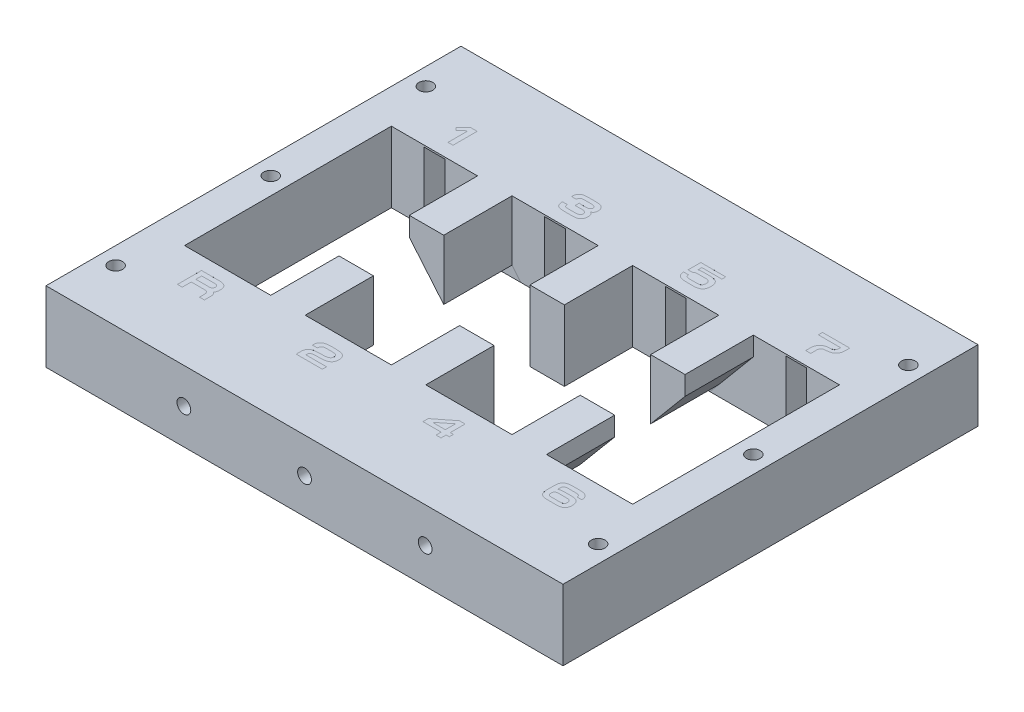
SolidWorks part; units mm, degrees
material "Oak"
ref_plane "Front Plane" through (0, 0, 0) normal (0, 0, 1) x (1, 0, 0)
ref_plane "Top Plane" through (0, 0, 0) normal (0, 1, 0) x (1, 0, 0)
ref_plane "Right Plane" through (0, 0, 0) normal (1, 0, 0) x (0, 0, -1)
sketch "Szkic3" plane through (0, 0, 0) normal (0, 1, 0) x (1, 0, 0)
  line L1 (-75, -60.2) -> (75, -60.2)
  line L2 (-75, -60.2) -> (-75, 60.2)
  line L3 (-75, 60.2) -> (75, 60.2)
  line L4 (75, -60.2) -> (75, 60.2)
  line L5 (-75, -60.2) -> (75, 60.2) construction
  line L6 (-75, 60.2) -> (75, -60.2) construction
  point P0 (0, 0)
extrude "Dodanie-wyciągnięcie1" add sketch "Szkic3" along normal blind 20.5 contours L2 L3 L4 L1
sketch "Szkic4" plane through (0, 20.5, 0) normal (0, 1, 0) x (1, 0, 0)
  line L0 (-65, 40.2) -> (-40, 40.2) construction
  line L1 (40, 40.2) -> (65, 40.2)
  line L2 (-30, 40.2) -> (-5, 40.2)
  line L3 (5, 40.2) -> (30, 40.2)
  line L4 (40, -40.2) -> (65, -40.2)
  line L5 (-65, -40.2) -> (-40, -40.2) construction
  line L6 (5, 40.2) -> (30, 40.2) construction
  line L7 (-65, 40.2) -> (-40, 40.2)
  line L8 (-65, 40.2) -> (-65, -40.2)
  line L9 (-65, -40.2) -> (-40, -40.2)
  line L10 (65, 40.2) -> (65, -40.2)
  line L12 (75, -60.2) -> (75, 60.2) construction
  line L19 (-5, 40.2) -> (-5, 10.2)
  line L20 (-5, 10.2) -> (5, 10.2)
  line L21 (5, 40.2) -> (5, 10.2)
  line L23 (30, 40.2) -> (30, 10.2)
  line L24 (30, 10.2) -> (40, 10.2)
  line L25 (40, 40.2) -> (40, 10.2)
  line L26 (-40, 40.2) -> (-40, 10.2)
  line L27 (-40, 10.2) -> (-30, 10.2)
  line L28 (-30, 40.2) -> (-30, 10.2)
  line L29 (-30, -40.2) -> (-5, -40.2)
  line L30 (5, -40.2) -> (30, -40.2)
  line L31 (-75, -60.2) -> (75, -60.2) construction
  line L32 (5, -40.2) -> (30, -40.2) construction
  line L41 (-5, -40.2) -> (-5, -10.2)
  line L42 (-5, -10.2) -> (5, -10.2)
  line L43 (5, -40.2) -> (5, -10.2)
  line L45 (30, -40.2) -> (30, -10.2)
  line L46 (30, -10.2) -> (40, -10.2)
  line L47 (40, -40.2) -> (40, -10.2)
  line L48 (-40, -40.2) -> (-40, -10.2)
  line L49 (-40, -10.2) -> (-30, -10.2)
  line L50 (-30, -40.2) -> (-30, -10.2)
  dimension "D1" = 25
  dimension "D4" = 10
  dimension "D2" = 30
  dimension "D3" = 10
  dimension "D5" = 80.4
  dimension "D6" = 20
  dimension "D7" = 30
  dimension "D8" = 30
  dimension "D9" = 30
  dimension "D10" = 30
  dimension "D11" = 30
extrude "Wytnij-wyciągnięcie1" cut sketch "Szkic4" against normal blind 20.5
sketch "Szkic5" plane through (0, 0, -40.2) normal (0, 0, 1) x (1, 0, 0)
  line L0 (-65, 0) -> (-65, 20.5) construction
  line L1 (-40, 0) -> (-65, 0)
  line L2 (-40, 0) -> (-40, 0.5)
  line L3 (-40, 0.5) -> (-65, 0.5)
  line L4 (-65, 0) -> (-65, 0.5)
extrude "Dodanie-wyciągnięcie2" add sketch "Szkic5" along normal blind 10.2
sketch "Szkic6" plane through (0, 0, -40.2) normal (0, 0, 1) x (1, 0, 0)
  line L0 (-40, 0.5) -> (-40, 20.5) construction
  line L1 (-65, 20.5) -> (-40, 20.5)
  line L2 (-65, 20.5) -> (-65, 20)
  line L3 (-65, 20) -> (-40, 20)
  line L4 (-40, 20.5) -> (-40, 20)
extrude "Dodanie-wyciągnięcie3" add sketch "Szkic6" along normal blind 10.2
sketch "Szkic7" plane through (-65, 0, 0) normal (1, 0, 0) x (0, 0, -1)
  line L1 (40.2, 0.5) -> (30, 0.5)
  line L2 (40.2, 0.5) -> (40.2, 20)
  line L3 (40.2, 20) -> (30, 20)
  line L4 (30, 0.5) -> (30, 20)
extrude "Dodanie-wyciągnięcie4" add sketch "Szkic7" along normal blind 9.5
sketch "Szkic8" plane through (-40, 0, 0) normal (-1, 0, 0) x (0, 0, 1)
  line L1 (-40.2, 0.5) -> (-30, 0.5)
  line L2 (-40.2, 0.5) -> (-40.2, 20)
  line L3 (-40.2, 20) -> (-30, 20)
  line L4 (-30, 0.5) -> (-30, 20)
extrude "Dodanie-wyciągnięcie5" add sketch "Szkic8" along normal blind 9.5
sketch "Szkic9" plane through (0, 0, -40.2) normal (0, 0, 1) x (1, 0, 0)
  line L0 (65, 0) -> (65, 20.5) construction
  line L1 (-30, 0) -> (65, 0)
  line L2 (-30, 0) -> (-30, 0.5)
  line L3 (-30, 0.5) -> (65, 0.5)
  line L4 (65, 0) -> (65, 0.5)
extrude "Dodanie-wyciągnięcie6" add sketch "Szkic9" along normal blind 10.2
sketch "Szkic10" plane through (0, 0, -40.2) normal (0, 0, 1) x (1, 0, 0)
  line L1 (-30, 20.5) -> (65, 20.5)
  line L2 (-30, 20.5) -> (-30, 20)
  line L3 (-30, 20) -> (65, 20)
  line L4 (65, 20.5) -> (65, 20)
extrude "Dodanie-wyciągnięcie7" add sketch "Szkic10" along normal blind 10.2
sketch "Szkic12" plane through (-5, 0, 0) normal (-1, 0, 0) x (0, 0, 1)
  line L1 (-40.2, 0.5) -> (-30, 0.5)
  line L2 (-40.2, 0.5) -> (-40.2, 20)
  line L3 (-40.2, 20) -> (-30, 20)
  line L4 (-30, 0.5) -> (-30, 20)
extrude "Dodanie-wyciągnięcie8" add sketch "Szkic12" along normal blind 9.5
sketch "Szkic13" plane through (-30, 0, 0) normal (1, 0, 0) x (0, 0, -1)
  line L1 (40.2, 0.5) -> (30, 0.5)
  line L2 (40.2, 0.5) -> (40.2, 20)
  line L3 (40.2, 20) -> (30, 20)
  line L4 (30, 0.5) -> (30, 20)
extrude "Dodanie-wyciągnięcie9" add sketch "Szkic13" along normal blind 9.5
sketch "Szkic14" plane through (5, 0, 0) normal (1, 0, 0) x (0, 0, -1)
  line L1 (40.2, 0.5) -> (30, 0.5)
  line L2 (40.2, 0.5) -> (40.2, 20)
  line L3 (40.2, 20) -> (30, 20)
  line L4 (30, 0.5) -> (30, 20)
extrude "Dodanie-wyciągnięcie10" add sketch "Szkic14" along normal blind 9.5
sketch "Szkic15" plane through (30, 0, 0) normal (-1, 0, 0) x (0, 0, 1)
  line L1 (-40.2, 0.5) -> (-30, 0.5)
  line L2 (-40.2, 0.5) -> (-40.2, 20)
  line L3 (-40.2, 20) -> (-30, 20)
  line L4 (-30, 0.5) -> (-30, 20)
extrude "Dodanie-wyciągnięcie11" add sketch "Szkic15" along normal blind 9.5
sketch "Szkic16" plane through (65, 0, 0) normal (-1, 0, 0) x (0, 0, 1)
  line L1 (-40.2, 0.5) -> (-30, 0.5)
  line L2 (-40.2, 0.5) -> (-40.2, 20)
  line L3 (-40.2, 20) -> (-30, 20)
  line L4 (-30, 0.5) -> (-30, 20)
extrude "Dodanie-wyciągnięcie12" add sketch "Szkic16" along normal blind 9.5
sketch "Szkic17" plane through (40, 0, 0) normal (1, 0, 0) x (0, 0, -1)
  line L1 (40.2, 0.5) -> (30, 0.5)
  line L2 (40.2, 0.5) -> (40.2, 20)
  line L3 (40.2, 20) -> (30, 20)
  line L4 (30, 0.5) -> (30, 20)
extrude "Dodanie-wyciągnięcie13" add sketch "Szkic17" along normal blind 9.5
sketch "Szkic18" plane through (0, 0, 40.2) normal (0, 0, -1) x (-1, 0, 0)
  line L0 (65, 0) -> (65, 20.5) construction
  line L1 (-65, 20.5) -> (65, 20.5)
  line L2 (-65, 20.5) -> (-65, 20)
  line L3 (-65, 20) -> (65, 20)
  line L4 (65, 20.5) -> (65, 20)
extrude "Dodanie-wyciągnięcie14" add sketch "Szkic18" along normal blind 10.2
sketch "Szkic19" plane through (0, 0, 40.2) normal (0, 0, -1) x (-1, 0, 0)
  line L1 (-65, 0) -> (65, 0)
  line L2 (-65, 0) -> (-65, 0.5)
  line L3 (-65, 0.5) -> (65, 0.5)
  line L4 (65, 0) -> (65, 0.5)
extrude "Dodanie-wyciągnięcie15" add sketch "Szkic19" along normal blind 10.2
sketch "Szkic20" plane through (65, 0, 0) normal (-1, 0, 0) x (0, 0, 1)
  line L1 (40.2, 0.5) -> (30, 0.5)
  line L2 (40.2, 0.5) -> (40.2, 20)
  line L3 (40.2, 20) -> (30, 20)
  line L4 (30, 0.5) -> (30, 20)
extrude "Dodanie-wyciągnięcie16" add sketch "Szkic20" along normal blind 9.5
sketch "Szkic21" plane through (40, 0, 0) normal (1, 0, 0) x (0, 0, -1)
  line L1 (-40.2, 0.5) -> (-30, 0.5)
  line L2 (-40.2, 0.5) -> (-40.2, 20)
  line L3 (-40.2, 20) -> (-30, 20)
  line L4 (-30, 0.5) -> (-30, 20)
extrude "Dodanie-wyciągnięcie17" add sketch "Szkic21" along normal blind 9.5
sketch "Szkic22" plane through (30, 0, 0) normal (-1, 0, 0) x (0, 0, 1)
  line L1 (40.2, 0.5) -> (30, 0.5)
  line L2 (40.2, 0.5) -> (40.2, 20)
  line L3 (40.2, 20) -> (30, 20)
  line L4 (30, 0.5) -> (30, 20)
extrude "Dodanie-wyciągnięcie18" add sketch "Szkic22" along normal blind 9.5
sketch "Szkic23" plane through (5, 0, 0) normal (1, 0, 0) x (0, 0, -1)
  line L1 (-40.2, 0.5) -> (-30, 0.5)
  line L2 (-40.2, 0.5) -> (-40.2, 20)
  line L3 (-40.2, 20) -> (-30, 20)
  line L4 (-30, 0.5) -> (-30, 20)
extrude "Dodanie-wyciągnięcie19" add sketch "Szkic23" along normal blind 9.5
sketch "Szkic24" plane through (-5, 0, 0) normal (-1, 0, 0) x (0, 0, 1)
  line L1 (40.2, 0.5) -> (30, 0.5)
  line L2 (40.2, 0.5) -> (40.2, 20)
  line L3 (40.2, 20) -> (30, 20)
  line L4 (30, 0.5) -> (30, 20)
extrude "Dodanie-wyciągnięcie20" add sketch "Szkic24" along normal blind 9.5
sketch "Szkic25" plane through (-30, 0, 0) normal (1, 0, 0) x (0, 0, -1)
  line L1 (-40.2, 0.5) -> (-30, 0.5)
  line L2 (-40.2, 0.5) -> (-40.2, 20)
  line L3 (-40.2, 20) -> (-30, 20)
  line L4 (-30, 0.5) -> (-30, 20)
extrude "Dodanie-wyciągnięcie21" add sketch "Szkic25" along normal blind 9.5
sketch "Szkic26" plane through (-40, 0, 0) normal (-1, 0, 0) x (0, 0, 1)
  line L1 (40.2, 0.5) -> (30, 0.5)
  line L2 (40.2, 0.5) -> (40.2, 20)
  line L3 (40.2, 20) -> (30, 20)
  line L4 (30, 0.5) -> (30, 20)
extrude "Dodanie-wyciągnięcie22" add sketch "Szkic26" along normal blind 9.5
sketch "Szkic27" plane through (-65, 0, 0) normal (1, 0, 0) x (0, 0, -1)
  line L1 (-40.2, 0.5) -> (-30, 0.5)
  line L2 (-40.2, 0.5) -> (-40.2, 20)
  line L3 (-40.2, 20) -> (-30, 20)
  line L4 (-30, 0.5) -> (-30, 20)
extrude "Dodanie-wyciągnięcie23" add sketch "Szkic27" along normal blind 9.5
sketch "Szkic28" plane through (0, 0, 40.2) normal (0, 0, -1) x (-1, 0, 0)
  line L0 (-52.5, 0.5) -> (-52.5, 1.5) construction
  line L1 (-49.5, 0.5) -> (-55.5, 0.5) construction
  line L2 (-52.5, 20) -> (-52.5, 19) construction
  line L3 (-55.5, 20) -> (-49.5, 20) construction
  line L4 (-52.5, 19) -> (-52.5, 1.5) construction
  line L5 (-49.5, 20) -> (-49.5, 0.5) construction
  line L6 (-55.5, 1.5) -> (-49.5, 1.5)
  line L7 (-55.5, 1.5) -> (-55.5, 19)
  line L8 (-55.5, 19) -> (-49.5, 19)
  line L9 (-49.5, 1.5) -> (-49.5, 19)
  line L10 (-55.5, 1.5) -> (-49.5, 19) construction
  line L11 (-55.5, 19) -> (-49.5, 1.5) construction
  point P8 (-52.5, 10.25)
extrude "Wytnij-wyciągnięcie2" cut sketch "Szkic28" against normal blind 10
sketch "Szkic29" plane through (0, 1.5, 0) normal (0, 1, 0) x (1, 0, 0)
  line L0 (52.5, -40.2) -> (52.5, -42.2) construction
  line L1 (55.5, -40.2) -> (49.5, -40.2) construction
  line L2 (52.5, -42.2) -> (52.5, -50.2) construction
  line L3 (55.5, -50.2) -> (49.5, -50.2) construction
  line L4 (49.5, -50.2) -> (49.5, -40.2) construction
  line L5 (55.5, -50.2) -> (49.5, -50.2)
  line L6 (55.5, -50.2) -> (55.5, -42.2)
  line L7 (55.5, -42.2) -> (49.5, -42.2)
  line L8 (49.5, -50.2) -> (49.5, -42.2)
  line L9 (55.5, -50.2) -> (49.5, -42.2) construction
  line L10 (55.5, -42.2) -> (49.5, -50.2) construction
  point P7 (52.5, -46.2)
extrude "Wytnij-wyciągnięcie3" cut sketch "Szkic29" against normal blind 10
sketch "Szkic32" plane through (0, 0, 40.2) normal (0, 0, -1) x (-1, 0, 0)
  line L0 (-17.5, 0.5) -> (-17.5, 1.5) construction
  line L1 (-14.5, 0.5) -> (-20.5, 0.5) construction
  line L2 (-14.5, 20) -> (-14.5, 0.5) construction
  line L3 (-14.5, 1.5) -> (-20.5, 1.5)
  line L4 (-14.5, 1.5) -> (-14.5, 20)
  line L5 (-14.5, 20) -> (-20.5, 20)
  line L6 (-20.5, 1.5) -> (-20.5, 20)
extrude "Wytnij-wyciągnięcie4" cut sketch "Szkic32" against normal blind 10
sketch "Szkic33" plane through (0, 1.5, 0) normal (0, 1, 0) x (1, 0, 0)
  line L0 (17.5, -40.2) -> (17.5, -42.2) construction
  line L1 (20.5, -40.2) -> (14.5, -40.2) construction
  line L2 (14.5, -50.2) -> (14.5, -40.2) construction
  line L3 (14.5, -42.2) -> (20.5, -42.2)
  line L4 (14.5, -42.2) -> (14.5, -50.2)
  line L5 (14.5, -50.2) -> (20.5, -50.2)
  line L6 (20.5, -42.2) -> (20.5, -50.2)
extrude "Wytnij-wyciągnięcie5" cut sketch "Szkic33" against normal blind 10
sketch "Szkic34" plane through (0, 0, 40.2) normal (0, 0, -1) x (-1, 0, 0)
  line L0 (17.5, 0.5) -> (17.5, 1.5) construction
  line L1 (20.5, 0.5) -> (14.5, 0.5) construction
  line L2 (20.5, 20) -> (20.5, 0.5) construction
  line L3 (20.5, 1.5) -> (14.5, 1.5)
  line L4 (20.5, 1.5) -> (20.5, 20)
  line L5 (20.5, 20) -> (14.5, 20)
  line L6 (14.5, 1.5) -> (14.5, 20)
extrude "Wytnij-wyciągnięcie6" cut sketch "Szkic34" against normal blind 10
sketch "Szkic35" plane through (0, 1.5, 0) normal (0, 1, 0) x (1, 0, 0)
  line L0 (-17.5, -40.2) -> (-17.5, -42.2) construction
  line L1 (-14.5, -40.2) -> (-20.5, -40.2) construction
  line L2 (-20.5, -50.2) -> (-20.5, -40.2) construction
  line L3 (-20.5, -42.2) -> (-14.5, -42.2)
  line L4 (-20.5, -42.2) -> (-20.5, -50.2)
  line L5 (-20.5, -50.2) -> (-14.5, -50.2)
  line L6 (-14.5, -42.2) -> (-14.5, -50.2)
extrude "Wytnij-wyciągnięcie7" cut sketch "Szkic35" against normal blind 10
sketch "Szkic36" plane through (0, 0, 40.2) normal (0, 0, -1) x (-1, 0, 0)
  line L0 (52.5, 0.5) -> (52.5, 1.5) construction
  line L1 (55.5, 0.5) -> (49.5, 0.5) construction
  line L2 (55.5, 20) -> (55.5, 0.5) construction
  line L3 (55.5, 1.5) -> (49.5, 1.5)
  line L4 (55.5, 1.5) -> (55.5, 20)
  line L5 (55.5, 20) -> (49.5, 20)
  line L6 (49.5, 1.5) -> (49.5, 20)
extrude "Wytnij-wyciągnięcie8" cut sketch "Szkic36" against normal blind 10
sketch "Szkic37" plane through (0, 1.5, 0) normal (0, 1, 0) x (1, 0, 0)
  line L0 (-52.5, -40.2) -> (-52.5, -42.2) construction
  line L1 (-49.5, -40.2) -> (-55.5, -40.2) construction
  line L2 (-55.5, -50.2) -> (-55.5, -40.2) construction
  line L3 (-55.5, -42.2) -> (-49.5, -42.2)
  line L4 (-55.5, -42.2) -> (-55.5, -50.2)
  line L5 (-55.5, -50.2) -> (-49.5, -50.2)
  line L6 (-49.5, -42.2) -> (-49.5, -50.2)
extrude "Wytnij-wyciągnięcie9" cut sketch "Szkic37" against normal blind 10
sketch "Szkic38" plane through (0, 0, -40.2) normal (0, 0, 1) x (1, 0, 0)
  line L0 (-52.5, 0.5) -> (-52.5, 1.5) construction
  line L1 (-49.5, 0.5) -> (-55.5, 0.5) construction
  line L2 (-49.5, 20) -> (-49.5, 0.5) construction
  line L3 (-49.5, 1.5) -> (-55.5, 1.5)
  line L4 (-49.5, 1.5) -> (-49.5, 20)
  line L5 (-49.5, 20) -> (-55.5, 20)
  line L6 (-55.5, 1.5) -> (-55.5, 20)
extrude "Wytnij-wyciągnięcie10" cut sketch "Szkic38" against normal blind 10
sketch "Szkic39" plane through (0, 1.5, 0) normal (0, 1, 0) x (1, 0, 0)
  line L0 (-52.5, 40.2) -> (-52.5, 42.2) construction
  line L1 (-55.5, 40.2) -> (-49.5, 40.2) construction
  line L2 (-49.5, 50.2) -> (-49.5, 40.2) construction
  line L3 (-49.5, 42.2) -> (-55.5, 42.2)
  line L4 (-49.5, 42.2) -> (-49.5, 50.2)
  line L5 (-49.5, 50.2) -> (-55.5, 50.2)
  line L6 (-55.5, 42.2) -> (-55.5, 50.2)
extrude "Wytnij-wyciągnięcie11" cut sketch "Szkic39" against normal blind 10
sketch "Szkic41" plane through (0, 0, -40.2) normal (0, 0, 1) x (1, 0, 0)
  line L0 (-17.5, 0.5) -> (-17.5, 1.5) construction
  line L1 (-14.5, 0.5) -> (-20.5, 0.5) construction
  line L2 (-14.5, 20) -> (-14.5, 0.5) construction
  line L3 (-14.5, 1.5) -> (-20.5, 1.5)
  line L4 (-14.5, 1.5) -> (-14.5, 20)
  line L5 (-14.5, 20) -> (-20.5, 20)
  line L6 (-20.5, 1.5) -> (-20.5, 20)
extrude "Wytnij-wyciągnięcie12" cut sketch "Szkic41" against normal blind 10
sketch "Szkic42" plane through (0, 1.5, 0) normal (0, 1, 0) x (1, 0, 0)
  line L0 (-17.5, 40.2) -> (-17.5, 42.2) construction
  line L1 (-20.5, 40.2) -> (-14.5, 40.2) construction
  line L2 (-14.5, 50.2) -> (-14.5, 40.2) construction
  line L3 (-14.5, 42.2) -> (-20.5, 42.2)
  line L4 (-14.5, 42.2) -> (-14.5, 50.2)
  line L5 (-14.5, 50.2) -> (-20.5, 50.2)
  line L6 (-20.5, 42.2) -> (-20.5, 50.2)
extrude "Wytnij-wyciągnięcie13" cut sketch "Szkic42" against normal blind 10
sketch "Szkic43" plane through (0, 0, -40.2) normal (0, 0, 1) x (1, 0, 0)
  line L0 (17.5, 0.5) -> (17.5, 1.5) construction
  line L1 (20.5, 0.5) -> (14.5, 0.5) construction
  line L2 (20.5, 20) -> (20.5, 0.5) construction
  line L3 (20.5, 1.5) -> (14.5, 1.5)
  line L4 (20.5, 1.5) -> (20.5, 20)
  line L5 (20.5, 20) -> (14.5, 20)
  line L6 (14.5, 1.5) -> (14.5, 20)
extrude "Wytnij-wyciągnięcie14" cut sketch "Szkic43" against normal blind 10
sketch "Szkic44" plane through (0, 1.5, 0) normal (0, 1, 0) x (1, 0, 0)
  line L0 (17.5, 40.2) -> (17.5, 42.2) construction
  line L1 (14.5, 40.2) -> (20.5, 40.2) construction
  line L2 (20.5, 50.2) -> (20.5, 40.2) construction
  line L3 (20.5, 42.2) -> (14.5, 42.2)
  line L4 (20.5, 42.2) -> (20.5, 50.2)
  line L5 (20.5, 50.2) -> (14.5, 50.2)
  line L6 (14.5, 42.2) -> (14.5, 50.2)
extrude "Wytnij-wyciągnięcie15" cut sketch "Szkic44" against normal blind 10
sketch "Szkic45" plane through (0, 0, -40.2) normal (0, 0, 1) x (1, 0, 0)
  line L0 (52.5, 0.5) -> (52.5, 1.5) construction
  line L1 (55.5, 0.5) -> (49.5, 0.5) construction
  line L2 (55.5, 20) -> (55.5, 0.5) construction
  line L3 (55.5, 1.5) -> (49.5, 1.5)
  line L4 (55.5, 1.5) -> (55.5, 20)
  line L5 (55.5, 20) -> (49.5, 20)
  line L6 (49.5, 1.5) -> (49.5, 20)
extrude "Wytnij-wyciągnięcie16" cut sketch "Szkic45" against normal blind 10
sketch "Szkic46" plane through (0, 1.5, 0) normal (0, 1, 0) x (1, 0, 0)
  line L0 (52.5, 40.2) -> (52.5, 42.2) construction
  line L1 (49.5, 40.2) -> (55.5, 40.2) construction
  line L2 (55.5, 50.2) -> (55.5, 40.2) construction
  line L3 (55.5, 42.2) -> (49.5, 42.2)
  line L4 (55.5, 42.2) -> (55.5, 50.2)
  line L5 (55.5, 50.2) -> (49.5, 50.2)
  line L6 (49.5, 42.2) -> (49.5, 50.2)
extrude "Wytnij-wyciągnięcie17" cut sketch "Szkic46" against normal blind 10
sketch "Szkic47" plane through (0, 20.5, 0) normal (0, 1, 0) x (1, 0, 0)
  line L0 (35, -10.2) -> (35, -60.2) construction
  line L1 (30, -10.2) -> (40, -10.2) construction
  line L2 (-75, -60.2) -> (75, -60.2) construction
  line L3 (0, -10.2) -> (0, -60.2) construction
  line L4 (-5, -10.2) -> (5, -10.2) construction
  line L5 (-35, -10.2) -> (-35, -60.2) construction
  line L6 (-40, -10.2) -> (-30, -10.2) construction
  line L7 (-35, 10.2) -> (-35, 60.2) construction
  line L8 (-30, 10.2) -> (-40, 10.2) construction
  line L9 (-75, 60.2) -> (75, 60.2) construction
  line L10 (0, 10.2) -> (0, 60.2) construction
  line L11 (5, 10.2) -> (-5, 10.2) construction
  line L12 (35, 10.2) -> (35, 60.2) construction
  line L13 (40, 10.2) -> (30, 10.2) construction
sketch "Szkic48" plane through (0, 0, 60.2) normal (0, 0, 1) x (1, 0, 0)
  line L0 (-35, 20.5) -> (-35, 0) construction
  line L1 (-75, 0) -> (75, 0) construction
  line L2 (0, 20.5) -> (0, 0) construction
  line L3 (-75, 20.5) -> (75, 20.5) construction
  line L4 (35, 20.5) -> (35, 0) construction
  circle A0 centre (-35, 10.25) radius 2
  circle A1 centre (0, 10.25) radius 2
  circle A2 centre (35, 10.25) radius 2
extrude "Wytnij-wyciągnięcie18" cut sketch "Szkic48" against normal blind 10
sketch "Szkic49" plane through (0, 0, -60.2) normal (0, 0, -1) x (-1, 0, 0)
  line L0 (-35, 20.5) -> (-35, 0) construction
  line L1 (75, 0) -> (-75, 0) construction
  line L2 (0, 20.5) -> (0, 0) construction
  line L3 (35, 20.5) -> (35, 0) construction
  circle A0 centre (-35, 10.25) radius 2
  circle A1 centre (0, 10.25) radius 2
  circle A2 centre (35, 10.25) radius 2
extrude "Wytnij-wyciągnięcie19" cut sketch "Szkic49" against normal blind 10
sketch "Szkic51" plane through (0, 20.5, 0) normal (0, 1, 0) x (1, 0, 0)
  line L0 (65, 0) -> (75, 0) construction
  line L1 (65, -30) -> (65, 30) construction
  line L2 (75, -60.2) -> (75, 60.2) construction
  line L3 (70, 0) -> (70, 45) construction
  line L4 (70, 0) -> (70, -45) construction
  circle A0 centre (70, 0) radius 2
  circle A1 centre (70, 45) radius 2
  circle A2 centre (70, -45) radius 2
extrude "Wytnij-wyciągnięcie20" cut sketch "Szkic51" against normal through all
sketch "Szkic52" plane through (0, 20.5, 0) normal (0, 1, 0) x (1, 0, 0)
  line L0 (-65, 0) -> (-75, 0) construction
  line L1 (-65, 30) -> (-65, -30) construction
  line L2 (-75, -60.2) -> (-75, 60.2) construction
  line L3 (-70, 0) -> (-70, -45) construction
  line L4 (-70, 0) -> (-70, 45) construction
  circle A0 centre (-70, 45) radius 2
  circle A1 centre (-70, 0) radius 2
  circle A2 centre (-70, -45) radius 2
extrude "Wytnij-wyciągnięcie21" cut sketch "Szkic52" against normal through all
sketch "Szkic53" plane through (0, 20.5, 0) normal (0, 1, 0) x (1, 0, 0)
  text T0 "1" font "MetroDF" height in points 22
  text T1 "2" font "MetroDF" height in points 22
  text T2 "3" font "MetroDF" height in points 22
  text T3 "5" font "MetroDF" height in points 22
  text T4 "7" font "MetroDF" height in points 22
  text T5 "R" font "MetroDF" height in points 22
  text T6 "4" font "MetroDF" height in points 22
  text T7 "6" font "MetroDF" height in points 22
extrude "Wytnij-wyciągnięcie22" cut sketch "Szkic53" against normal blind 0.001
chamfer "Sfazowanie1" distance 15 angle 40 1 edges at (-40, 0, 20.1) first distance on face at (-40, 10.25, 20.1)
chamfer "Sfazowanie2" distance 15 angle 40 1 edges at (-40, 0, -20.1) first distance on face at (-40, 10.25, -20.1)
chamfer "Sfazowanie3" distance 15 angle 40 1 edges at (40, 0, -20.1) first distance on face at (40, 10.25, -20.1)
chamfer "Sfazowanie4" distance 15 angle 40 1 edges at (40, 0, 20.1) first distance on face at (40, 10.25, 20.1)
